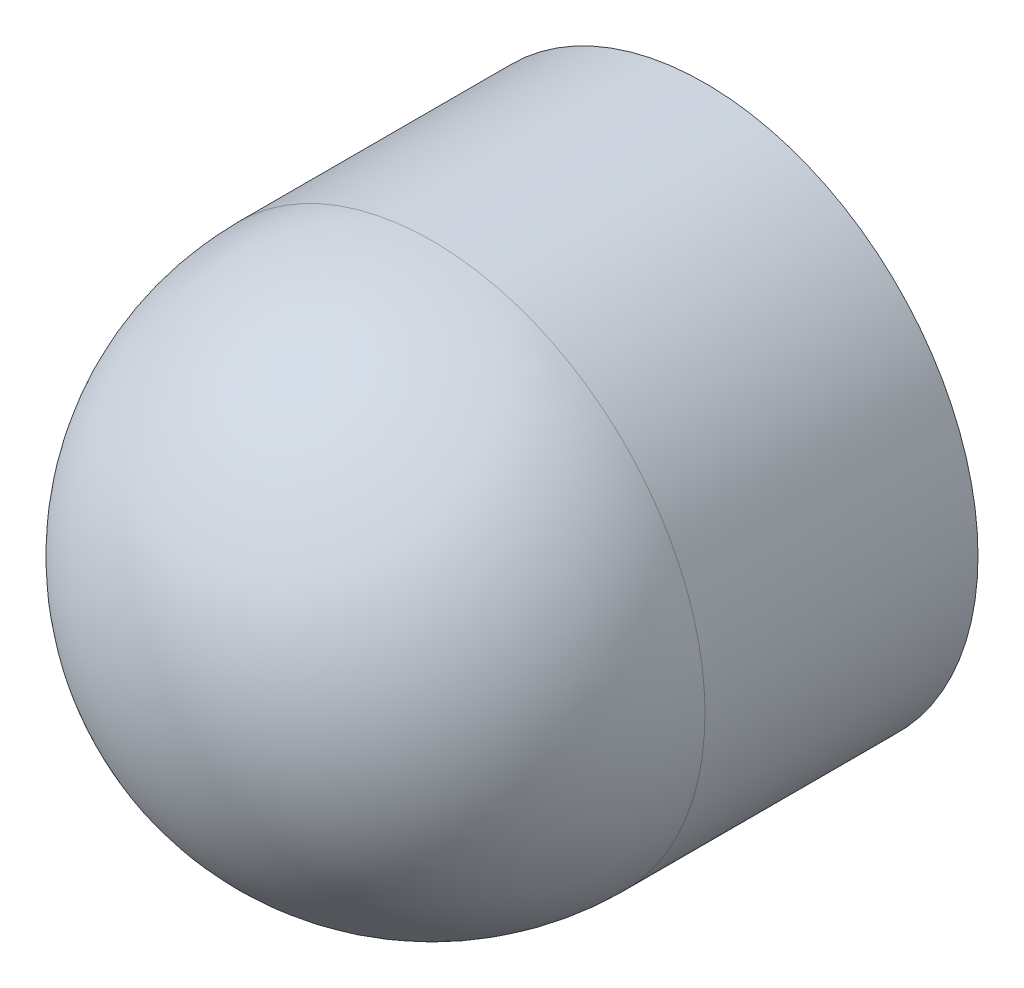
SolidWorks part; units mm, degrees
material "Plastique personnalisé"
ref_plane "Plan de face" through (0, 0, 0) normal (0, 0, 1) x (1, 0, 0)
ref_plane "Plan de dessus" through (0, 0, 0) normal (0, 1, 0) x (1, 0, 0)
ref_plane "Plan de droite" through (0, 0, 0) normal (1, 0, 0) x (0, 0, -1)
sketch "Esquisse1" plane through (0, 0, 0) normal (0, 0, 1) x (1, 0, 0)
  circle A0 centre (0, 0) radius 10
extrude "Boss.-Extru.1" add sketch "Esquisse1" along normal blind 10
dome "Dôme1" faces to dome 1 distance 10 reverse direction no elliptical dome no face at (10, 0, 10) parameters "D1"=10
sketch "Esquisse2" plane through (0, 0, 0) normal (0, 0, -1) x (-1, 0, 0)
  circle A0 centre (0, 0) radius 2.52
extrude "Enlèv. mat.-Extru.1" cut sketch "Esquisse2" against normal blind 10
